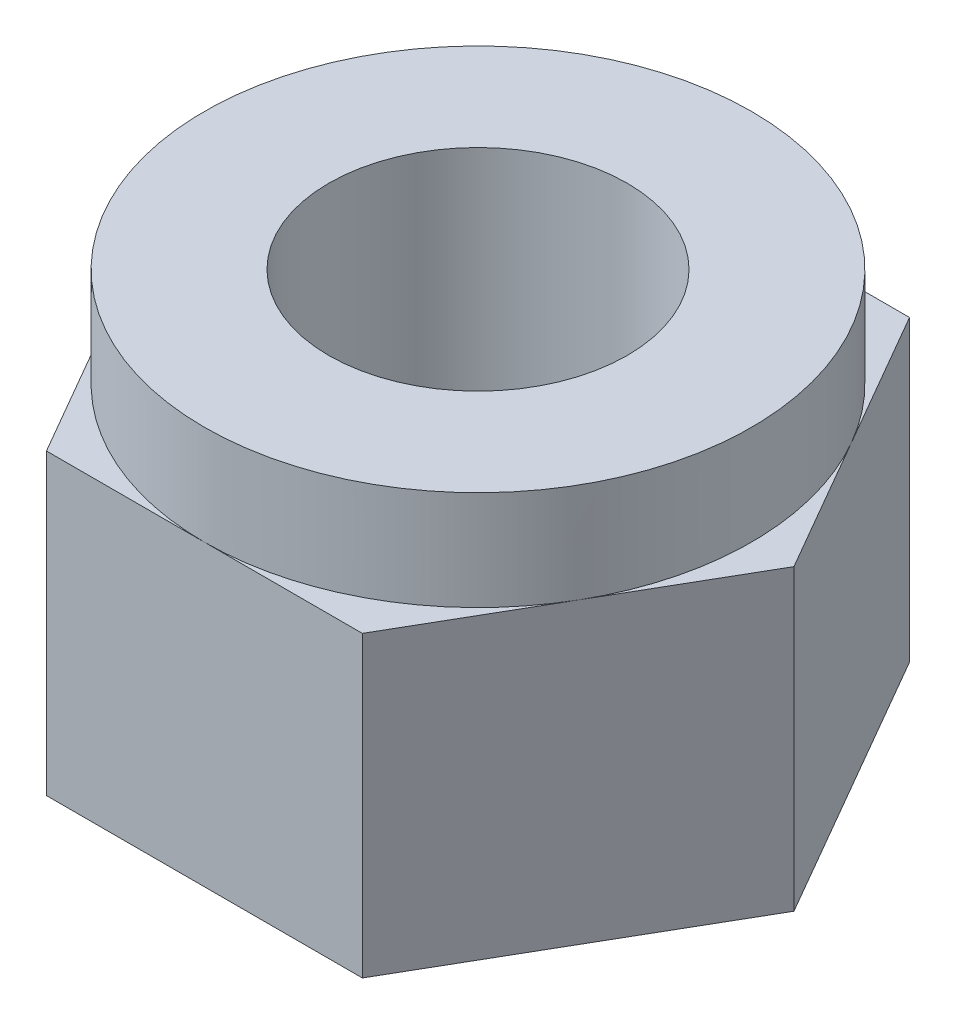
SolidWorks part; units mm, degrees
ref_plane "前视基准面" through (0, 0, 0) normal (0, 0, 1) x (1, 0, 0)
ref_plane "上视基准面" through (0, 0, 0) normal (0, 1, 0) x (1, 0, 0)
ref_plane "右视基准面" through (0, 0, 0) normal (1, 0, 0) x (0, 0, -1)
other "Configuration Table"
sketch "草图1" plane through (0, 0, 0) normal (0, 1, 0) x (1, 0, 0)
  line L1 (3.1754, 0) -> (1.5877, 2.75)
  line L2 (1.5877, 2.75) -> (-1.5877, 2.75)
  line L3 (-1.5877, 2.75) -> (-3.1754, 0)
  line L4 (-3.1754, 0) -> (-1.5877, -2.75)
  line L5 (-1.5877, -2.75) -> (1.5877, -2.75)
  line L6 (1.5877, -2.75) -> (3.1754, 0)
  circle A0 centre (0, 0) radius 2.75 construction
  dimension "D1" = 5.5
extrude "凸台-拉伸1" add sketch "草图1" along normal blind 3
sketch "草图2" plane through (0, 3, 0) normal (0, 1, 0) x (1, 0, 0)
  line L0 (1.5877, -2.75) -> (3.1754, 0) construction
  circle A0 centre (0, 0) radius 2.75
extrude "凸台-拉伸2" add sketch "草图2" along normal blind 1
sketch "草图3" plane through (0, 0, 0) normal (0, -1, 0) x (1, 0, 0)
  circle A0 centre (0, 0) radius 1.5
  dimension "D1" = 3
extrude "切除-拉伸1" cut sketch "草图3" against normal through all
ref_axis "基准轴1" through (0, 7.2881, 0) along (0, -1, 0)
